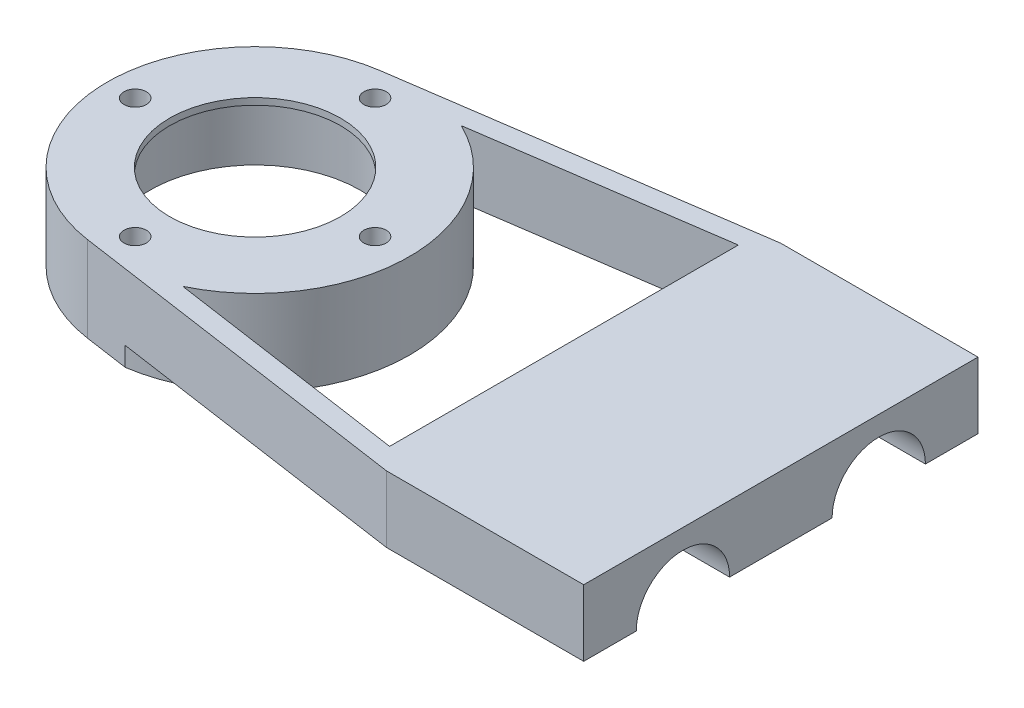
SolidWorks part; units mm, degrees
material "3.1355 (EN-AW 2024)"
ref_plane "Front" through (0, 0, 0) normal (0, 0, 1) x (1, 0, 0)
ref_plane "Top" through (0, 0, 0) normal (0, 1, 0) x (1, 0, 0)
ref_plane "Right" through (0, 0, 0) normal (1, 0, 0) x (0, 0, -1)
sketch "Эскиз1" plane through (0, 0, 0) normal (0, 1, 0) x (1, 0, 0)
  line L0 (0, 0) -> (0, 60)
  line L1 (0, 60) -> (-30, 60)
  line L2 (0, 30) -> (-130, 30) construction
  line L3 (-30, 60) -> (-30, 30) construction
  line L4 (-30, 60) -> (-83.2348, 52.2663)
  line L5 (-30, 0) -> (-83.2348, 7.7337)
  line L6 (0, 0) -> (-30, 0)
  circle A0 centre (-80, 30) radius 22.5 construction
  arc A1 (-83.2348, 52.2663) -> (-83.2348, 7.7337) centre (-80, 30) ccw
  dimension "D2" = 45
  dimension "D1" = 60
  dimension "D3" = 30
  dimension "D4" = 130
  dimension "D5" = 50
extrude "Бобышка-Вытянуть1" add sketch "Эскиз1" along normal blind 13
sketch "Эскиз2" plane through (0, 0, 0) normal (0, -1, 0) x (1, 0, 0)
  circle A0 centre (-80, -30) radius 16
  dimension "D1" = 32
extrude "Вырез-Вытянуть1" cut sketch "Эскиз2" against normal offset from surface (12 mm away) 1 up to face at (-40.9558, 13, -30)
sketch "Эскиз3" plane through (0, 12, 0) normal (0, -1, 0) x (1, 0, 0)
  circle A0 centre (-80, -30) radius 13
  dimension "D1" = 26
extrude "Вырез-Вытянуть2" cut sketch "Эскиз3" against normal through all
sketch "Эскиз4" plane through (0, 0, 0) normal (0, -1, 0) x (1, 0, 0)
  circle A0 centre (-80, -30) radius 20.5
  dimension "D1" = 41
extrude "Вырез-Вытянуть3" cut sketch "Эскиз4" against normal offset from surface (2 mm away) 10 up to face at (-80, 12, -43)
sketch "Эскиз5" plane through (0, 2, 0) normal (0, -1, 0) x (1, 0, 0)
  circle A0 centre (-80, -30) radius 18.25 construction
  circle A1 centre (-80, -30) radius 20.5 construction
  dimension "D1" = 36.5
hole_wizard "Отверстие с зазором M31" positions "Эскиз7" profile "Эскиз6" hole size "M3" standard "Ansi Metric" end condition through all
sketch "Эскиз7" plane through (0, 2, 0) normal (0, -1, 0) x (-1, 0, 0)
  line L0 (0, 30) -> (130, 30) construction
  circle A0 centre (80, 30) radius 18.25 construction
  point P0 (80, 11.75)
  point P4 (98.25, 30)
  point P8 (80, 48.25)
  point P10 (61.75, 30)
sketch "Эскиз6" plane through (-80, 2, -11.75) normal (1, 0, 0) x (0, 0, -1)
  line L0 (0, 0) -> (0, 11)
  line L1 (0, 11) -> (1.7, 11)
  line L2 (1.7, 11) -> (1.7, 0)
  line L5 (1.7, 0) -> (0, 0)
  line L11 (0, -6.35) -> (0, 107.95) construction
  dimension "Диаметр сквозного отверстия" = 3.4
  dimension "Глубина сквозного отверстия" = 11
sketch "Эскиз8" plane through (0, 0, 0) normal (1, 0, 0) x (0, 0, -1)
  line L0 (30, 13) -> (30, 0) construction
  line L1 (8, 2.9) -> (0, 2.9)
  line L2 (0, 13) -> (60, 13) construction
  line L3 (52, 2.9) -> (60, 2.9)
  line L4 (22.2, 2.9) -> (37.8, 2.9)
  line L5 (52.5, 0) -> (7.5, 0) construction
  line L6 (0, 13) -> (0, 0) construction
  line L7 (51.3807, 0) -> (60, 0)
  line L8 (21.5807, 0) -> (38.4193, 0)
  line L18 (0, 0) -> (60, 0)
  line L19 (60, 0) -> (60, 13)
  line L20 (60, 13) -> (0, 13)
  line L21 (0, 13) -> (0, 0)
  line L22 (0, 0) -> (8.6193, 0)
  line L23 (60, 0) -> (60, 2.9)
  line L25 (0, 2.9) -> (0, 0)
  circle A0 centre (15.1, 2.9) radius 7.1
  circle A1 centre (44.9, 2.9) radius 7.1
  line M3 (0, 0) -> (60, 0)
  line M4 (60, 0) -> (60, 13)
  line M6 (0, 13) -> (0, 0)
  dimension "D1" = 14.2
  dimension "D3" = 10.1
  dimension "D4" = 0
  dimension "D2" = 15.1
extrude "Вырез-Вытянуть8" cut sketch "Эскиз8" against normal blind 30 contours A0 M3 | A0 L1 M6 M3 | L4 L0 L8 A1 | A1 M3 | L3 A1 M3 M4 | L0 L4 A0 M3 region at (0, 1.4315, -34.0034) region at (0, 1.4315, -25.9966) region at (0, 4.4225, -15.1) region at (0, 4.4225, -44.9) region at (0, 1.4319, -55.8966) region at (0, 1.4319, -4.1034)
sketch "Эскиз12" plane through (0, 0, 0) normal (0, -1, 0) x (1, 0, 0)
  line L0 (-30, 0) -> (-83.2348, -7.7337) construction
  line L1 (-30, -60) -> (-83.2348, -52.2663) construction
  line L2 (-30, -60) -> (-30, -30) construction
  line L3 (-30, 0) -> (-76.5229, -6.7587)
  line L4 (-30, -60) -> (-76.5229, -53.2413)
  line L5 (-30, -60) -> (-30, 0)
  circle A2 centre (-80, -30) radius 23.5
  arc A3 (-76.5229, -53.2413) -> (-76.5229, -6.7587) centre (-80, -30) ccw
  dimension "D1" = 3
extrude "Вырез-Вытянуть9" cut sketch "Эскиз12" against normal up to surface (2.9 mm away) up to face at (-15, 2.9, -4)
sketch "Эскиз13" plane through (0, 2.9, 0) normal (0, -1, 0) x (1, 0, 0)
  line L26 (-3, -34.8) -> (-3, -25.2)
  line L27 (-3, -25.2) -> (-33, -25.2)
  line L28 (-33, -25.2) -> (-33, -5)
  line L29 (-33, -5) -> (-3, -5)
  line L30 (-3, -5) -> (-3, -3)
  line L31 (-3, -3) -> (-29.7832, -3)
  line L32 (-29.7832, -3) -> (-65.0455, -8.1228)
  line L33 (-65.0455, -51.8772) -> (-29.7832, -57)
  line L34 (-29.7832, -57) -> (-3, -57)
  line L35 (-3, -57) -> (-3, -55)
  line L36 (-3, -55) -> (-33, -55)
  line L37 (-33, -55) -> (-33, -34.8)
  line L38 (-33, -34.8) -> (-3, -34.8)
  line L45 (-33, -3.4673) -> (-69.8248, -8.8171)
  line L46 (-69.8248, -51.1829) -> (-33, -56.5327)
  line L50 (-33, -56.5327) -> (-33, -3.4673)
  arc A0 (-76.5229, -53.2413) -> (-76.5229, -6.7587) centre (-80, -30) ccw construction
  arc A1 (-69.8248, -51.1829) -> (-69.8248, -8.8171) centre (-80, -30) ccw
  arc A2 (-65.0455, -51.8772) -> (-65.0455, -8.1228) centre (-80, -30) ccw
  dimension "D1" = 3
extrude "Вырез-Вытянуть10" cut sketch "Эскиз13" against normal through all
equation "\"D4@Эскиз1\"=\"D3@Эскиз1\"+100"
equation "\"D1@Эскиз5\"=32+4.5"
equation "\"D2@Эскиз8\"=8+\"D1@Эскиз8\"/2"
equation "\"D3@Эскиз8\"=3+\"D1@Эскиз8\"/2"
